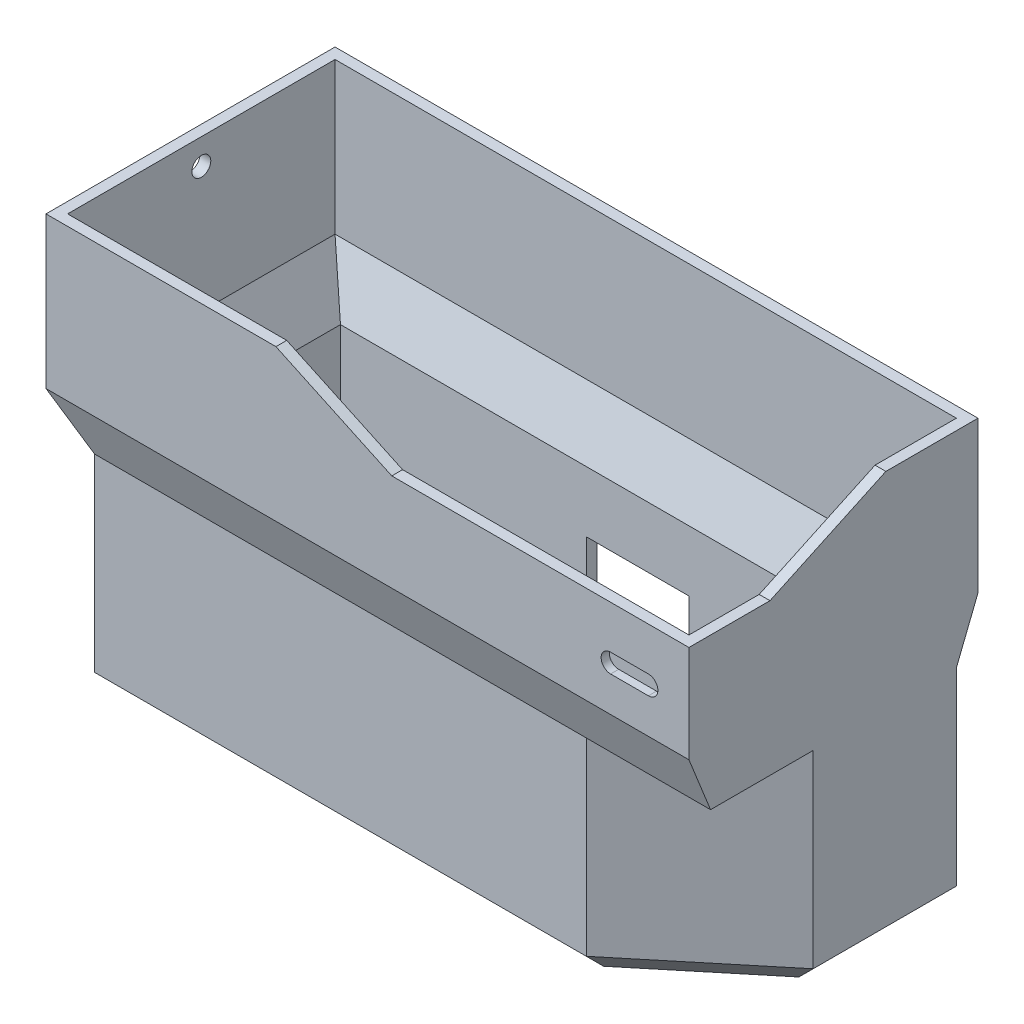
SolidWorks part; units mm, degrees
ref_plane "Plano frontal" through (0, 0, 0) normal (0, 0, 1) x (1, 0, 0)
ref_plane "Plano superior" through (0, 0, 0) normal (0, 1, 0) x (1, 0, 0)
ref_plane "Plano direito" through (0, 0, 0) normal (1, 0, 0) x (0, 0, -1)
sketch "Esboço1" plane through (0, 0, 0) normal (0, 1, 0) x (1, 0, 0)
  line L0 (-59.25, 26.75) -> (59.25, 26.75)
  line L1 (-57.25, -24.75) -> (59.25, -24.75)
  line L2 (-57.25, -24.75) -> (-57.25, 24.75)
  line L3 (-57.25, 24.75) -> (59.25, 24.75)
  line L4 (57.25, -24.75) -> (57.25, 24.75) construction
  line L5 (-57.25, -24.75) -> (57.25, 24.75) construction
  line L6 (-57.25, 24.75) -> (57.25, -24.75) construction
  line L7 (59.25, -26.75) -> (59.25, -24.75)
  line L8 (-59.25, -26.75) -> (59.25, -26.75)
  line L10 (-57.25, 24.75) -> (57.25, 24.75) construction
  line L11 (-57.25, -24.75) -> (57.25, -24.75) construction
  line L12 (-59.25, -26.75) -> (-59.25, 26.75)
  line L13 (-59.25, -26.75) -> (-59.25, 26.75) construction
  line L14 (59.25, 24.75) -> (59.25, 26.75)
  line L15 (59.25, -26.75) -> (59.25, 26.75) construction
  point P0 (0, 0)
  dimension "D1" = 114.5
  dimension "D2" = 49.5
  dimension "D3" = 2
extrude "Ressalto-extrusão1" add sketch "Esboço1" along normal blind 28
sketch "Esboço3" plane through (-59.25, 0, 0) normal (1, 0, 0) x (0, 0, -1)
  line L0 (0, 0) -> (0, 28) construction
  line L1 (-26.75, 28) -> (-24.75, 28) construction
  line L2 (-26.75, 0) -> (-24.75, 0) construction
  line L3 (-24.75, 28) -> (24.75, 28) construction
  circle A0 centre (0, 23.25) radius 1.75
  circle A1 centre (0, 4.75) radius 1.75 construction
  dimension "D1" = 3.5
  dimension "D2" = 4.75
  dimension "D3" = 4.75
extrude "Corte-extrusão1" cut sketch "Esboço3" along normal through all contours A0 | A1
ref_plane "Plano1" through (0, -10, 0) normal (0, -1, 0) x (-1, 0, 0)
sketch "Esboço6" plane through (0, -10, 0) normal (0, -1, 0) x (-1, 0, 0)
  line L0 (59.25, 26.75) -> (59.25, -26.75) construction
  line L1 (-59.25, 22.75) -> (54.25, 22.75)
  line L2 (-54.25, 22.75) -> (-54.25, 20.75) construction
  line L3 (-59.25, -22.75) -> (54.25, -22.75)
  line L4 (54.25, 22.75) -> (54.25, -22.75)
  line L5 (-54.25, 22.75) -> (54.25, -22.75) construction
  line L6 (-54.25, -22.75) -> (54.25, 22.75) construction
  line L7 (-59.25, -22.75) -> (-59.25, -20.75)
  line L8 (52.25, 20.75) -> (52.25, -20.75)
  line L9 (-59.25, -20.75) -> (52.25, -20.75)
  line L11 (-59.25, 20.75) -> (52.25, 20.75)
  line L12 (-52.25, 20.75) -> (52.25, 20.75) construction
  line L13 (-52.25, -20.75) -> (52.25, -20.75) construction
  line L14 (-52.25, 20.75) -> (-52.25, -20.75) construction
  line L15 (-54.25, -20.75) -> (-54.25, -22.75) construction
  line L16 (-54.25, 22.75) -> (-54.25, -22.75) construction
  line L17 (-59.25, 26.75) -> (59.25, 26.75) construction
  line L18 (-54.25, 22.75) -> (54.25, 22.75) construction
  line L19 (-54.25, -22.75) -> (54.25, -22.75) construction
  line L20 (-59.25, 20.75) -> (-59.25, 22.75)
  line L21 (-59.25, 24.75) -> (-59.25, 26.75) construction
  point P0 (0, 0)
  dimension "D1" = 5
  dimension "D2" = 2
  dimension "D3" = 4
loft "Loft1" add profiles "Esboço6" section face at (0.5, 0, 0) section "Esboço6"
sketch "Esboço7" plane through (59.25, 0, 0) normal (1, 0, 0) x (0, 0, -1)
  line L0 (-26.75, 28) -> (26.75, 28)
  line L1 (26.75, 28) -> (26.75, 0)
  line L2 (26.75, 0) -> (22.75, -10)
  line L3 (22.75, -10) -> (-22.75, -10)
  line L4 (-22.75, -10) -> (-26.75, 0)
  line L5 (-26.75, 0) -> (-26.75, 28)
extrude "Ressalto-extrusão3" add sketch "Esboço7" against normal blind 1.5
sketch "Esboço22" plane through (59.25, 0, 0) normal (1, 0, 0) x (0, 0, -1)
  line L6 (-26.75, 28) -> (-26.75, 0)
  line L7 (-26.75, 0) -> (-22.75, -10)
  line L8 (-22.75, -10) -> (22.75, -10)
  line L9 (22.75, -10) -> (26.75, 0)
  line L10 (26.75, 0) -> (26.75, 28)
  line L11 (26.75, 28) -> (-26.75, 28)
  line L12 (-26.75, 28) -> (-26.75, 0)
  line L13 (-26.75, 0) -> (-22.75, -10)
  line L14 (-22.75, -10) -> (22.75, -10)
  line L15 (22.75, -10) -> (26.75, 0)
  line L16 (26.75, 0) -> (26.75, 28)
  line L17 (26.75, 28) -> (-26.75, 28)
  dimension "D1" = 0
extrude "Ressalto-extrusão9" add sketch "Esboço22" along normal blind 0.5
sketch "Esboço8" plane through (0, -10, 0) normal (0, -1, 0) x (1, 0, 0)
  line L0 (57.75, 20.75) -> (57.75, -20.75) construction
  line L1 (57.75, -20.75) -> (-52.25, -20.75) construction
  line L2 (-52.25, -20.75) -> (-52.25, 20.75) construction
  line L3 (-52.25, 20.75) -> (57.75, 20.75) construction
  line L4 (59.25, 22.75) -> (-54.25, 22.75)
  line L5 (-54.25, 22.75) -> (-54.25, -22.75)
  line L6 (-54.25, -22.75) -> (59.25, -22.75)
  line L7 (59.25, -22.75) -> (59.75, -22.75)
  line L8 (59.25, 22.75) -> (-54.25, 22.75)
  line L9 (-54.25, 22.75) -> (-54.25, -22.75)
  line L10 (-54.25, -22.75) -> (59.25, -22.75)
  line L12 (57.75, 20.75) -> (57.75, -20.75)
  line L13 (57.75, -20.75) -> (-52.25, -20.75)
  line L14 (-52.25, -20.75) -> (-52.25, 20.75)
  line L15 (-52.25, 20.75) -> (57.75, 20.75)
  line L22 (59.25, -22.75) -> (59.75, -22.75)
  line L23 (59.75, -22.75) -> (59.75, 22.75)
  line L24 (59.75, -22.75) -> (59.75, 22.75)
  line L25 (59.75, 22.75) -> (59.25, 22.75)
  line L26 (59.75, 22.75) -> (59.25, 22.75)
  dimension "D1" = 0
extrude "Ressalto-extrusão4" add sketch "Esboço8" along normal blind 40
sketch "Esboço10" plane through (0, -50, 0) normal (0, -1, 0) x (1, 0, 0)
  line L0 (59.75, 26.75) -> (36.75, 26.75)
  line L1 (59.75, -22.75) -> (59.75, 22.75) construction
  line L2 (36.75, 26.75) -> (36.75, 3.75)
  line L3 (36.75, 3.75) -> (59.75, 3.75)
  line L5 (59.75, 3.75) -> (59.75, 26.75)
  line L6 (-59.25, 26.75) -> (59.75, 26.75) construction
  point P2 (0, 0)
  dimension "D1" = 23
  dimension "D2" = 23
extrude "Corte-extrusão3" cut sketch "Esboço10" against normal blind 40
sketch "Esboço11" plane through (0, -10, 0) normal (0, -1, 0) x (1, 0, 0)
  line L0 (36.75, 20.75) -> (57.75, 3.75)
  line L1 (57.75, 3.75) -> (59.75, 3.75)
  line L2 (59.75, 3.75) -> (59.75, 22.75)
  line L3 (59.75, 22.75) -> (36.75, 22.75)
  line L4 (36.75, 22.75) -> (36.75, 20.75)
  line L5 (59.75, -26.75) -> (59.75, 26.75) construction
  line L6 (59.25, 22.75) -> (36.75, 22.75) construction
  line L7 (57.75, 3.75) -> (59.75, 3.75) construction
  line L8 (57.75, -20.75) -> (57.75, 3.75) construction
  point P4 (0, 0)
  point P8 (58.7312, 2.6688)
  point P12 (57.75, 3.75)
extrude "Ressalto-extrusão5" add sketch "Esboço11" against normal blind 2
sketch "Esboço12" plane through (0, -50, 0) normal (0, -1, 0) x (1, 0, 0)
  line L0 (36.75, 22.75) -> (59.75, 3.75)
  line L1 (59.75, 3.75) -> (57.75, 3.75)
  line L2 (57.75, 3.75) -> (36.75, 20.75)
  line L3 (36.75, 20.75) -> (36.75, 22.75) construction
  line L4 (57.75, -20.75) -> (57.75, 3.75) construction
  line L5 (36.75, 22.75) -> (34.8375, 22.75)
  line L6 (36.75, 22.75) -> (-54.25, 22.75) construction
  line L7 (34.8375, 22.75) -> (34.8375, 20.75)
  line L8 (36.75, 20.75) -> (-52.25, 20.75) construction
  line L9 (34.8375, 20.75) -> (36.75, 20.75)
extrude "Ressalto-extrusão6" add sketch "Esboço12" against normal up to surface (40 mm away) up to face at (51.8333, -10, 17.6667)
sketch "Esboço13" plane through (0, -50, 0) normal (0, -1, 0) x (1, 0, 0)
  line L5 (59.75, -22.75) -> (59.75, 3.75)
  line L6 (59.75, 3.75) -> (36.75, 22.75)
  line L7 (36.75, 22.75) -> (-54.25, 22.75)
  line L8 (-54.25, 22.75) -> (-54.25, -22.75)
  line L9 (-54.25, -22.75) -> (59.75, -22.75)
  line L11 (59.75, 3.75) -> (36.75, 22.75)
  line L12 (36.75, 22.75) -> (-54.25, 22.75)
  line L13 (-54.25, 22.75) -> (-54.25, -22.75)
  line L14 (-54.25, -22.75) -> (59.75, -22.75)
  line L15 (59.75, -22.75) -> (59.75, 3.75)
  dimension "D1" = 0
extrude "Ressalto-extrusão7" add sketch "Esboço13" against normal blind 1.5
sketch "Esboço14" plane through (0, 0, 26.75) normal (0, 0, 1) x (1, 0, 0)
  line L0 (-59.25, 28) -> (59.75, 28) construction
  line L1 (51.25, 23.25) -> (51.25, 8.25) construction
  line L3 (41.4494, 8.25) -> (58.75, 8.25) construction
  line L4 (52.25, 8.25) -> (45.25, 8.25) construction
  line L5 (52.25, 6.5) -> (45.25, 6.5)
  line L6 (52.25, 10) -> (45.25, 10)
  line L7 (59.75, 28) -> (59.75, 0) construction
  circle A0 centre (51.25, 23.25) radius 1.75 construction
  circle A1 centre (51.25, 8.25) radius 1.75 construction
  arc A2 (52.25, 6.5) -> (52.25, 10) centre (52.25, 8.25) ccw
  arc A3 (45.25, 10) -> (45.25, 6.5) centre (45.25, 8.25) ccw
  point P10 (48.75, 8.25)
  point P17 (0, 0)
  dimension "D1" = 4.75
  dimension "D2" = 3.5
  dimension "D4" = 1
  dimension "D3" = 15
  dimension "D5" = 7
  dimension "D6" = 1
  dimension "D7" = 7.5
extrude "Corte-extrusão4" cut sketch "Esboço14" against normal blind 1.5
sketch "Esboço15" plane through (0, -48.5, 0) normal (0, 1, 0) x (1, 0, 0)
  line L5 (-52.25, 20.75) -> (-52.25, -20.75)
  line L6 (-52.25, -20.75) -> (36.75, -20.75)
  line L7 (36.75, -20.75) -> (57.75, -3.75)
  line L8 (57.75, -3.75) -> (57.75, 20.75)
  line L9 (57.75, 20.75) -> (-52.25, 20.75)
  line L10 (-52.25, 20.75) -> (-52.25, -20.75)
  line L11 (-52.25, -20.75) -> (36.75, -20.75)
  line L12 (36.75, -20.75) -> (57.75, -3.75)
  line L13 (57.75, -3.75) -> (57.75, 20.75)
  line L14 (57.75, 20.75) -> (-52.25, 20.75)
  dimension "D1" = 0
extrude "Ressalto-extrusão8" add sketch "Esboço15" along normal blind 20
chamfer "Chanfro1" distance 5 angle 45 5 edges at (2.75, -50, -22.75) (-54.25, -50, 0) (-8.75, -50, 22.75) (48.25, -50, 13.25) (59.75, -50, -9.5)
shell "Casca1" thickness 2
sketch "Esboço17" plane through (0, -50, 0) normal (0, -1, 0) x (1, 0, 0)
  line L0 (5, 12) -> (-5, 12) construction
  line L1 (5, 8) -> (-5, 8)
  line L2 (5, 16) -> (-5, 16)
  line L3 (0, 12) -> (0, 0) construction
  arc A1 (5, 8) -> (5, 16) centre (5, 12) ccw
  arc A2 (-5, 16) -> (-5, 8) centre (-5, 12) ccw
  point P2 (0, 12)
  dimension "D1" = 4
  dimension "D2" = 12
  dimension "D3" = 10
extrude "Corte-extrusão6" cut sketch "Esboço17" against normal blind 2
sketch "Esboço18" plane through (0, 0, -22.75) normal (0, 0, -1) x (-1, 0, 0)
  line L0 (-59.75, -27.5) -> (54.25, -27.5) construction
  line L2 (54.25, -45) -> (54.25, -10) construction
  line L3 (-59.75, -45) -> (-59.75, -10) construction
  line L4 (-12.25, -21.25) -> (6.75, -21.25)
  line L5 (-12.25, -21.25) -> (-12.25, -33.75)
  line L6 (-12.25, -33.75) -> (6.75, -33.75)
  line L7 (6.75, -21.25) -> (6.75, -33.75)
  line L8 (-12.25, -21.25) -> (6.75, -33.75) construction
  line L9 (-12.25, -33.75) -> (6.75, -21.25) construction
  point P2 (-59.75, -27.5)
  point P6 (-2.75, -27.5)
  dimension "D1" = 12.5
  dimension "D2" = 19
extrude "Corte-extrusão7" cut sketch "Esboço18" against normal blind 2
sketch "Esboço19" plane through (0, 0, 26.75) normal (0, 0, 1) x (1, 0, 0)
  line L0 (59.75, 18) -> (4.75, 18)
  line L2 (4.75, 18) -> (-16.6951, 28)
  line L3 (-59.25, 28) -> (59.75, 28) construction
  line L4 (-16.6951, 28) -> (59.75, 28)
  line L5 (59.75, 28) -> (59.75, 18)
  line L6 (59.75, 0) -> (59.75, 28) construction
  point P2 (0, 0)
  point P4 (0, 0)
  dimension "D1" = 10
  dimension "D2" = 25
  dimension "D3" = 55
extrude "Corte-extrusão8" cut sketch "Esboço19" against normal blind 2 contours L2 L4 L5 L0
sketch "Esboço20" plane through (59.75, 0, 0) normal (1, 0, 0) x (0, 0, -1)
  line L0 (-26.75, 18) -> (-11.75, 18)
  line L1 (-11.75, 18) -> (9.6951, 28)
  line L3 (9.6951, 28) -> (-26.75, 28)
  line L4 (-26.75, 28) -> (-26.75, 18)
  line L5 (-26.75, 28) -> (-26.75, 18) construction
  line L6 (-24.75, 18) -> (-26.75, 18) construction
  line L7 (26.75, 28) -> (-24.75, 28) construction
  point P3 (0, 0)
  point P9 (0, 0)
  point P14 (0, 0)
  dimension "D1" = 25
  dimension "D2" = 15
extrude "Corte-extrusão9" cut sketch "Esboço20" against normal blind 2
sketch "Esboço21" plane through (-54.25, 0, 0) normal (-1, 0, 0) x (0, 0, 1)
  line L0 (-22.75, -27.5) -> (22.75, -27.5) construction
  line L1 (-22.75, -45) -> (-22.75, -10) construction
  line L2 (22.75, -45) -> (22.75, -10) construction
  line L4 (-13.5, -38) -> (13.5, -38)
  line L5 (-13.5, -38) -> (-13.5, -17)
  line L6 (-13.5, -17) -> (13.5, -17)
  line L7 (13.5, -38) -> (13.5, -17)
  line L8 (-13.5, -38) -> (13.5, -17) construction
  line L9 (-13.5, -17) -> (13.5, -38) construction
  point P6 (0, -27.5)
  dimension "D1" = 27
  dimension "D2" = 21
extrude "Corte-extrusão10" cut sketch "Esboço21" against normal blind 2
